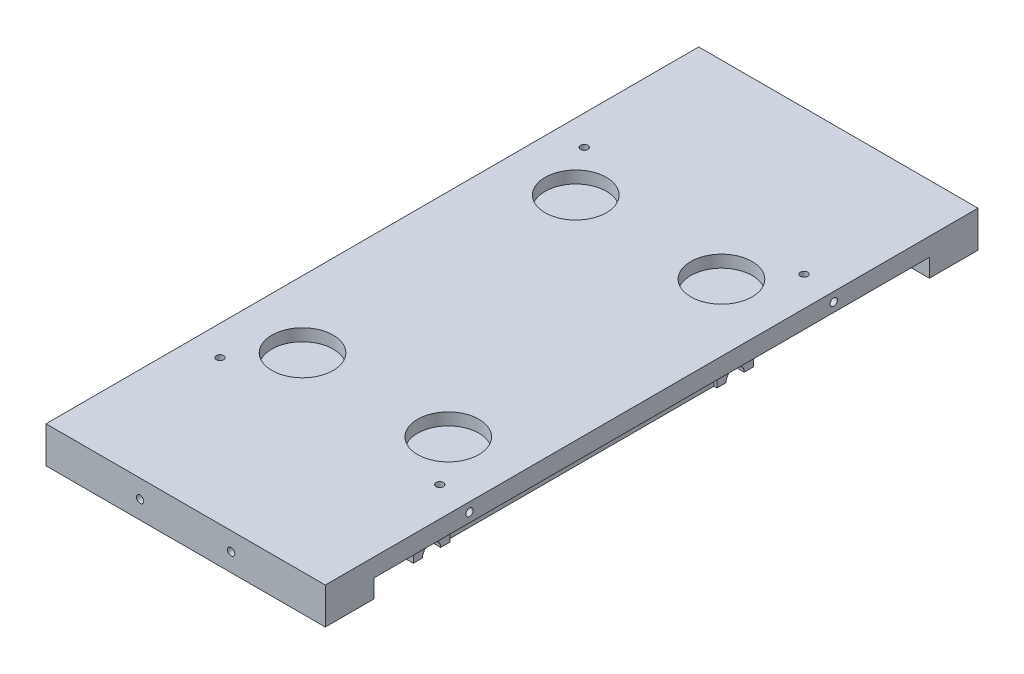
SolidWorks part; units mm, degrees
other "标注1"
sketch "草图3" plane through (-22.25, 4, -10) normal (-0.231, 0.6469, -0.7268) x (-0.9696, -0.2151, 0.1167)
ref_plane "前视基准面" through (0, 0, 0) normal (0, 0, 1) x (1, 0, 0)
ref_plane "上视基准面" through (0, 0, 0) normal (0, 1, 0) x (1, 0, 0)
ref_plane "右视基准面" through (0, 0, 0) normal (1, 0, 0) x (0, 0, -1)
other "Configuration Table"
sketch "草图4" plane through (0, 0, 0) normal (0, 1, 0) x (1, 0, 0)
  line L1 (-23, -53.75) -> (23, -53.75)
  line L2 (-23, -53.75) -> (-23, 53.75)
  line L3 (-23, 53.75) -> (23, 53.75)
  line L4 (23, -53.75) -> (23, 53.75)
  line L5 (-23, -53.75) -> (23, 53.75) construction
  line L6 (-23, 53.75) -> (23, -53.75) construction
  point P0 (0, 0)
  dimension "D1" = 107.5
  dimension "D2" = 46
extrude "凸台-拉伸1" add sketch "草图4" along normal blind 3
sketch "草图5" plane through (0, 0, 0) normal (0, -1, 0) x (1, 0, 0)
  line L0 (-11.75, 28) -> (11.75, -28) construction
  line L1 (-11.75, 28) -> (11.75, 28)
  line L2 (-11.75, 28) -> (-11.75, -28)
  line L3 (-11.75, -28) -> (11.75, -28)
  line L4 (11.75, 28) -> (11.75, -28)
  dimension "D1" = 56
  dimension "D2" = 23.5
extrude "凸台-拉伸2" add sketch "草图5" along normal blind 12.4
sketch "草图6" plane through (-11.75, 0, 0) normal (-1, 0, 0) x (0, 0, 1)
  line L0 (28, -12.4) -> (-28, -12.4) construction
  line L1 (-25, -12.4) -> (25, -12.4)
  circle A2 centre (25, -12.4) radius 0.75
  circle A3 centre (25, -12.4) radius 1.5
  circle A4 centre (-25, -12.4) radius 0.75
  circle A5 centre (-25, -12.4) radius 1.5
  dimension "D3" = 1.5
  dimension "D4" = 3
  dimension "D5" = 50
extrude "切除-拉伸1" cut sketch "草图6" against normal through all contours A4 | A2
extrude "切除-拉伸4" cut sketch "草图6<5>" against normal blind 1.2 contours A3 | A5
sketch "草图6<5>" plane through (-11.75, 0, 0) normal (-1, 0, 0) x (0, 0, 1) same geometry as "草图6"
extrude "切除-拉伸5" cut sketch "草图6<6>" along normal blind 1.2 from surface contours A3 | A5 starting at face at (11.75, -9.1125, 0)
sketch "草图6<6>" plane through (-11.75, 0, 0) normal (-1, 0, 0) x (0, 0, 1) same geometry as "草图6"
sketch "草图7" plane through (0, -12.4, 0) normal (0, -1, 0) x (-1, 0, 0)
  line L0 (9.2499, -6) -> (9.2499, 6) construction
  line L1 (-9.2499, -20) -> (-9.2499, 20) construction
  line L2 (9.2499, 0) -> (-9.2499, 0) construction
  circle A0 centre (9.2499, -20) radius 0.7
  circle A1 centre (-9.2499, -20) radius 0.7
  circle A2 centre (-9.2499, -6) radius 0.7
  circle A3 centre (9.2499, -6) radius 0.7
  circle A4 centre (9.2499, 6) radius 0.7
  circle A5 centre (-9.2499, 6) radius 0.7
  circle A6 centre (-9.2499, 20) radius 0.7
  circle A7 centre (9.2499, 20) radius 0.7
  dimension "D1" = 1.4
  dimension "D2" = 18.4999
  dimension "D3" = 12
  dimension "D4" = 40
extrude "切除-拉伸6" cut sketch "草图7" against normal blind 2
sketch "草图9" plane through (0, 0, 0) normal (0, -1, 0) x (1, 0, 0)
  line L0 (-23, 53.75) -> (23, 53.75) construction
  line L1 (-23, 53.75) -> (23, 53.75)
  line L2 (-23, 53.75) -> (-23, 45.75)
  line L3 (-23, 45.75) -> (23, 45.75)
  line L4 (23, 53.75) -> (23, 45.75)
  line L5 (23, 53.75) -> (23, -53.75) construction
  line L6 (23, -53.75) -> (-23, -53.75) construction
  line L7 (-23, -53.75) -> (23, -53.75)
  line L8 (-23, -53.75) -> (-23, -45.75)
  line L9 (-23, -45.75) -> (23, -45.75)
  line L10 (23, -53.75) -> (23, -45.75)
  line L11 (-23, -53.75) -> (-23, 53.75) construction
  line L12 (-23, 41.9103) -> (-20, 41.9103) construction
  line L13 (-20, 45.75) -> (-23, 45.75)
  line L14 (-20, 45.75) -> (-20, -45.75)
  line L15 (-20, -45.75) -> (-23, -45.75)
  line L16 (-23, 45.75) -> (-23, -45.75)
  line L17 (23, -45.75) -> (20, -45.75)
  line L18 (23, -45.75) -> (23, 45.75)
  line L19 (23, 45.75) -> (20, 45.75)
  line L20 (20, -45.75) -> (20, 45.75)
  line L22 (20, 41.9103) -> (23, 41.9103) construction
  line M17 (23, -53.75) -> (23, 53.75)
  line M18 (23, 53.75) -> (-23, 53.75)
  line M19 (-23, 53.75) -> (-23, -53.75)
  line M20 (-23, -53.75) -> (23, -53.75)
  dimension "D1" = 8
  dimension "D2" = 3
extrude "凸台-拉伸3" add sketch "草图9" along normal blind 3 contours L3 M19 M17 M18 | L9 M19 M20 M17 region at (0, 0, 49.75) region at (0, 0, -49.75)
sketch "草图10" plane through (0, 0, 53.75) normal (0, 0, 1) x (1, 0, 0)
  line L1 (-7.5, 0) -> (7.5, 0) construction
  circle A0 centre (-7.5, 0) radius 0.6
  circle A1 centre (7.5, 0) radius 0.6
  dimension "D2" = 1.2
  dimension "D1" = 15
extrude "切除-拉伸8" cut sketch "草图10" against normal blind 2
extrude "切除-拉伸9" cut sketch "草图10<2>" along normal blind 2 from surface starting at face at (0, 0, -53.75)
sketch "草图10<2>" plane through (0, 0, 53.75) normal (0, 0, 1) x (1, 0, 0) same geometry as "草图10"
sketch "草图11" plane through (0, 3, 0) normal (0, 1, 0) x (1, 0, 0)
  line L0 (-18.1, 30) -> (-18.1, -30) construction
  line L1 (-18.1, -30) -> (18.1, -30) construction
  line L2 (18.1, -30) -> (18.1, 30) construction
  line L3 (18.1, 30) -> (-18.1, 30) construction
  line L4 (-18.1, 0) -> (18.1, 0) construction
  circle A0 centre (-18.1, 30) radius 0.6
  circle A1 centre (18.1, 30) radius 0.6
  circle A2 centre (18.1, -30) radius 0.6
  circle A3 centre (-18.1, -30) radius 0.6
  dimension "D1" = 1.2
  dimension "D2" = 60
  dimension "D3" = 36.2
extrude "切除-拉伸10" cut sketch "草图11" against normal blind 2
sketch "草图12" plane through (-11.75, 0, 0) normal (-1, 0, 0) x (0, 0, 1)
  line L0 (23.5, -12.4) -> (-23.5, -12.4) construction
  line L1 (-22, -12.4) -> (22, -12.4)
  line L2 (-22, -12.4) -> (-22, 0)
  line L3 (-22, 0) -> (22, 0)
  line L4 (22, -12.4) -> (22, 0)
  line L5 (28, 0) -> (-28, 0) construction
  line L6 (-28, -12.4) -> (-22, -12.4) construction
  line L7 (-26.5, -12.4) -> (-28, -12.4) construction
  line L8 (22, -12.4) -> (28, -12.4) construction
  line L9 (28, -12.4) -> (28, 0) construction
  line L10 (-28, -12.4) -> (-28, 0) construction
  circle A0 centre (-25, -12.4) radius 0.75 construction
  arc A2 (-23.5, -12.4) -> (-26.5, -12.4) centre (-25, -12.4) ccw construction
  circle A3 centre (25, -12.4) radius 1.5 construction
  arc A4 (26.5, -12.4) -> (23.5, -12.4) centre (25, -12.4) ccw construction
extrude "切除-拉伸11" cut sketch "草图12" against normal blind 0.5
extrude "切除-拉伸12" cut sketch "草图12<2>" along normal blind 0.5 from surface starting at face at (11.75, -8.925, 0)
sketch "草图12<2>" plane through (-11.75, 0, 0) normal (-1, 0, 0) x (0, 0, 1) same geometry as "草图12"
sketch "草图13" plane through (23, 0, 0) normal (1, 0, 0) x (0, 0, -1)
  line L0 (0, 0) -> (0, 3) construction
  line L1 (-45.75, 0) -> (45.75, 0) construction
  line L2 (-53.75, 3) -> (53.75, 3) construction
  line L3 (-30, 1.5) -> (0, 1.5) construction
  line L4 (0, 1.5) -> (30, 1.5) construction
  circle A0 centre (-30, 1.5) radius 0.6
  circle A1 centre (30, 1.5) radius 0.6
  dimension "D1" = 1.2
  dimension "D2" = 30
extrude "切除-拉伸13" cut sketch "草图13" against normal blind 2
extrude "切除-拉伸14" cut sketch "草图13<2>" along normal blind 2 from surface starting at face at (-23, -0.75, 0)
sketch "草图13<2>" plane through (23, 0, 0) normal (1, 0, 0) x (0, 0, -1) same geometry as "草图13"
sketch "草图14" plane through (0, 3, 0) normal (0, 1, 0) x (1, 0, 0)
  line L0 (-12, 22.5) -> (12, 22.5) construction
  line L1 (12, 22.5) -> (12, -22.5) construction
  line L2 (12, -22.5) -> (-12, -22.5) construction
  line L3 (-12, -22.5) -> (-12, 22.5) construction
  line L4 (0, 22.5) -> (0, 0) construction
  line L5 (-12, 0) -> (0, 0) construction
  circle A0 centre (-12, 22.5) radius 5.05
  circle A1 centre (12, 22.5) radius 5.05
  circle A2 centre (-12, -22.5) radius 5.05
  circle A3 centre (12, -22.5) radius 5.05
  dimension "D1" = 10.1
  dimension "D2" = 24
  dimension "D3" = 45
extrude "切除-拉伸15" cut sketch "草图14" against normal blind 2
